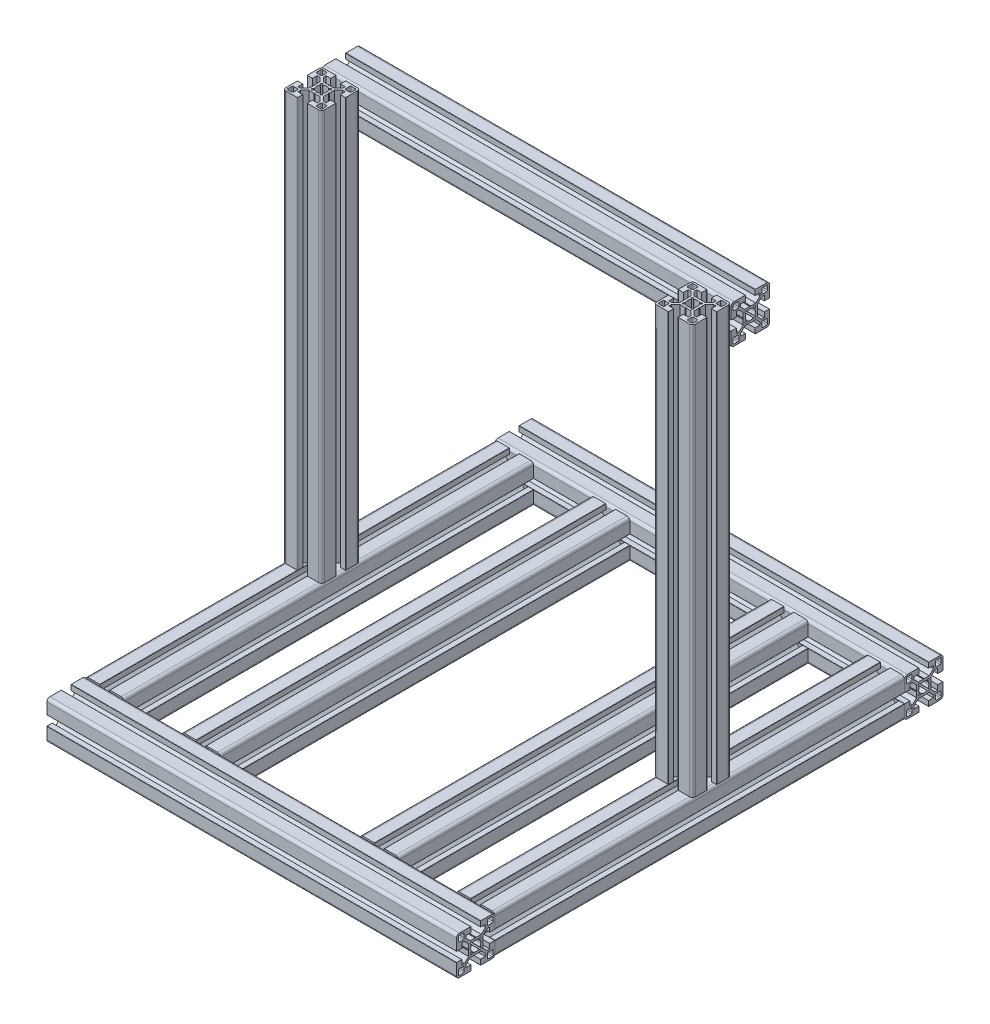
SolidWorks part; units mm, degrees
note: The reader was unsure of these and kept them because the rebuilt part matched: shared geometry of "Sketch3<2>", "Sketch5<2>".
ref_plane "Front Plane" through (0, 0, 0) normal (0, 0, 1) x (1, 0, 0)
ref_plane "Top Plane" through (0, 0, 0) normal (0, 1, 0) x (1, 0, 0)
ref_plane "Right Plane" through (0, 0, 0) normal (1, 0, 0) x (0, 0, -1)
sketch3d "3DSketch1"
  line L0 (-112.5, 0, -212.5) -> (-112.5, 0, 212.5)
  line L1 (-212.5, 0, -212.5) -> (212.5, 0, -212.5)
  line L2 (-212.5, 0, -212.5) -> (-212.5, 0, 212.5)
  line L3 (-212.5, 0, 212.5) -> (212.5, 0, 212.5)
  line L4 (212.5, 0, -212.5) -> (212.5, 0, 212.5)
  line L5 (-212.5, 0, -212.5) -> (212.5, 0, 212.5) construction
  line L6 (-212.5, 0, 212.5) -> (212.5, 0, -212.5) construction
  line L7 (112.5, 0, -212.5) -> (112.5, 0, 212.5)
  line L8 (212.5, 0, -12.5) -> (212.5, 425, -12.5)
  line L9 (-212.5, 0, -12.5) -> (-212.5, 425, -12.5)
  line L10 (212.5, 425, -12.5) -> (-212.5, 425, -12.5)
  line L11 (-212.5, 425, -12.5) -> (-212.5, 425, -32.5)
  line L13 (-212.5, 425, -32.5) -> (212.5, 425, -32.5)
  line L14 (212.5, 425, -12.5) -> (212.5, 425, -32.5)
  point P0 (0, 0, 0)
  dimension "D1" = 425
  dimension "D2" = 425
  dimension "D3" = 100
  dimension "D4" = 100
  dimension "D5" = 425
  dimension "D6" = 425
  dimension "D7" = 200
  dimension "D8" = 200
  dimension "D9" = 425
  dimension "D10" = 20
other "Lengths 1" corner treatment butt2
ref_plane "Plane2" through (-242.5, -70, -212.5) normal (0, 0, 1) x (1, 0, 0)
sketch "Profile" plane through (-242.5, -70, -212.5) normal (0, 0, 1) x (1, 0, 0)
  line L11 (37, 68) -> (33, 68)
  line L12 (69.7, 55) -> (64.5, 55)
  line L13 (64.5, 60) -> (64.5, 55)
  line L14 (70, 67) -> (70, 55.3)
  line L15 (68, 67) -> (68, 63)
  line L16 (64.5, 40) -> (64.5, 45)
  line L17 (69.7, 45) -> (64.5, 45)
  line L18 (70, 33) -> (70, 44.7)
  line L19 (68, 33) -> (68, 37)
  line L20 (33, 70) -> (44.7, 70)
  line L21 (60, 64.5) -> (60, 61.7678)
  line L22 (60, 64.5) -> (55, 64.5)
  line L23 (60, 61.7678) -> (55.7322, 57.5)
  line L24 (61.7678, 60) -> (57.5, 55.7322)
  line L25 (40, 64.5) -> (40, 61.7678)
  line L26 (40, 64.5) -> (45, 64.5)
  line L27 (40, 61.7678) -> (44.2678, 57.5)
  line L28 (35.5, 60) -> (38.2322, 60)
  line L29 (30.3, 55) -> (35.5, 55)
  line L30 (38.2322, 60) -> (42.5, 55.7322)
  line L31 (35.5, 55) -> (35.5, 60)
  line L32 (30, 67) -> (30, 55.3)
  line L33 (32, 67) -> (32, 63)
  line L34 (38, 67) -> (38, 63)
  line L35 (45, 69.7) -> (45, 64.5)
  line L36 (55, 69.7) -> (55, 64.5)
  line L37 (62, 67) -> (62, 63)
  line L38 (61.7678, 40) -> (57.5, 44.2678)
  line L39 (60, 35.5) -> (60, 38.2322)
  line L40 (60, 38.2322) -> (55.7322, 42.5)
  line L41 (55, 30.3) -> (55, 35.5)
  line L42 (62, 33) -> (62, 37)
  line L43 (38.2322, 40) -> (42.5, 44.2678)
  line L44 (40, 35.5) -> (40, 38.2322)
  line L45 (40, 35.5) -> (45, 35.5)
  line L46 (44.2678, 42.5) -> (49.4804, 42.5)
  line L47 (40, 38.2322) -> (44.2678, 42.5)
  line L48 (35.5, 45) -> (35.5, 40)
  line L49 (30.3, 45) -> (35.5, 45)
  line L50 (33, 38) -> (37, 38)
  line L51 (35.5, 40) -> (38.2322, 40)
  line L52 (33, 32) -> (37, 32)
  line L53 (33, 30) -> (44.7, 30)
  line L54 (30, 33) -> (30, 44.7)
  line L55 (32, 33) -> (32, 37)
  line L56 (38, 33) -> (38, 37)
  line L57 (45, 30.3) -> (45, 35.5)
  line L58 (50, 75) -> (50, 25) construction
  line L59 (57.5, 55.7322) -> (57.5, 50.5196)
  line L60 (67, 38) -> (63, 38)
  line L61 (25, 50) -> (75, 50) construction
  line L62 (64.5, 40) -> (61.7678, 40)
  line L63 (67, 62) -> (63, 62)
  line L64 (64.5, 60) -> (61.7678, 60)
  line L65 (42.5, 44.2678) -> (42.5, 49.4804)
  line L66 (37, 62) -> (33, 62)
  line L67 (44.2678, 57.5) -> (49.4804, 57.5)
  line L68 (57.5, 49.4804) -> (57.5, 44.2678)
  line L69 (42.5, 50.5196) -> (42.5, 55.7322)
  line L70 (50.5196, 57.5) -> (55.7322, 57.5)
  line L71 (55.3, 70) -> (67, 70)
  line L72 (63, 68) -> (67, 68)
  line L73 (55.3, 30) -> (67, 30)
  line L74 (63, 32) -> (67, 32)
  line L75 (55, 35.5) -> (60, 35.5)
  line L76 (50.5196, 42.5) -> (55.7322, 42.5)
  line L77 (57.2, 50) -> (57.5, 50.5196)
  line L78 (57.2, 50) -> (57.5, 49.4804)
  line L79 (42.8, 50) -> (42.5, 50.5196)
  line L80 (42.8, 50) -> (42.5, 49.4804)
  line L81 (50, 57.2) -> (49.4804, 57.5)
  line L82 (50, 57.2) -> (50.5196, 57.5)
  line L83 (50, 42.8) -> (49.4804, 42.5)
  line L84 (50, 42.8) -> (50.5196, 42.5)
  arc A0 (69.7, 55) -> (70, 55.3) centre (69.7, 55.3) ccw
  arc A1 (68, 67) -> (67, 68) centre (67, 67) ccw
  arc A2 (70, 44.7) -> (69.7, 45) centre (69.7, 44.7) ccw
  arc A3 (68, 37) -> (67, 38) centre (67, 37) ccw
  arc A4 (62, 63) -> (63, 62) centre (63, 63) ccw
  arc A5 (30, 55.3) -> (30.3, 55) centre (30.3, 55.3) ccw
  arc A6 (37, 62) -> (38, 63) centre (37, 63) ccw
  arc A7 (38, 67) -> (37, 68) centre (37, 67) ccw
  arc A8 (62, 33) -> (63, 32) centre (63, 33) ccw
  arc A9 (30.3, 45) -> (30, 44.7) centre (30.3, 44.7) ccw
  arc A10 (38, 37) -> (37, 38) centre (37, 37) ccw
  arc A11 (32, 33) -> (33, 32) centre (33, 33) ccw
  arc A12 (37, 32) -> (38, 33) centre (37, 33) ccw
  arc A13 (33, 38) -> (32, 37) centre (33, 37) ccw
  arc A14 (63, 38) -> (62, 37) centre (63, 37) ccw
  arc A15 (67, 62) -> (68, 63) centre (67, 63) ccw
  arc A16 (30, 33) -> (33, 30) centre (33, 33) ccw
  arc A17 (44.7, 30) -> (45, 30.3) centre (44.7, 30.3) ccw
  arc A18 (32, 63) -> (33, 62) centre (33, 63) ccw
  arc A19 (33, 68) -> (32, 67) centre (33, 67) ccw
  arc A20 (45, 69.7) -> (44.7, 70) centre (44.7, 69.7) ccw
  arc A21 (33, 70) -> (30, 67) centre (33, 67) ccw
  arc A22 (63, 68) -> (62, 67) centre (63, 67) ccw
  arc A23 (67, 32) -> (68, 33) centre (67, 33) ccw
  arc A24 (55, 30.3) -> (55.3, 30) centre (55.3, 30.3) ccw
  arc A25 (55.3, 70) -> (55, 69.7) centre (55.3, 69.7) ccw
  arc A26 (67, 30) -> (70, 33) centre (67, 33) ccw
  arc A27 (70, 67) -> (67, 70) centre (67, 67) ccw
  arc A28 (45.694, 53.0035) -> (45.694, 46.9966) centre (50, 50) ccw
  arc A29 (46.9981, 45.6929) -> (53.0039, 45.6943) centre (50, 50) ccw
  arc A30 (54.3061, 46.9967) -> (54.3061, 53.0034) centre (50, 50) ccw
  arc A31 (53.0033, 54.3061) -> (46.9968, 54.3062) centre (50, 50) ccw
  arc A32 (46.4038, 54.6058) -> (45.3944, 53.5962) centre (45.4038, 54.5962) ccw
  arc A33 (54.608, 53.5963) -> (53.5962, 54.6065) centre (54.5962, 54.5962) ccw
  arc A34 (53.5962, 45.3942) -> (54.6061, 46.4038) centre (54.5962, 45.4038) ccw
  arc A35 (45.3939, 46.4038) -> (46.4038, 45.3942) centre (45.4038, 45.4038) ccw
  arc A36 (45.694, 53.0035) -> (45.3944, 53.5962) centre (45.3778, 53.2158) ccw
  arc A37 (46.4038, 54.6058) -> (46.9968, 54.3062) centre (46.7842, 54.6222) ccw
  arc A38 (54.608, 53.5963) -> (54.3061, 53.0034) centre (54.6221, 53.2158) ccw
  arc A39 (53.0033, 54.3061) -> (53.5962, 54.6065) centre (53.2158, 54.6221) ccw
  arc A40 (45.3939, 46.4038) -> (45.694, 46.9966) centre (45.3778, 46.7842) ccw
  arc A41 (46.9981, 45.6929) -> (46.4038, 45.3942) centre (46.7842, 45.3779) ccw
  arc A42 (54.3061, 46.9967) -> (54.6061, 46.4038) centre (54.6222, 46.7842) ccw
  arc A43 (53.5962, 45.3942) -> (53.0039, 45.6943) centre (53.2158, 45.3778) ccw
  point P109 (30, 70)
  point P110 (30, 30)
  point P111 (70, 30)
  point P112 (70, 70)
  point P113 (0, 0)
other "Lengths 2" corner treatment butt2
ref_plane "Plane3" through (42.5, -70, -212.5) normal (0, 0, 1) x (1, 0, 0)
sketch "Profile1" plane through (42.5, -70, -212.5) normal (0, 0, 1) x (1, 0, 0)
  line L11 (37, 68) -> (33, 68)
  line L12 (69.7, 55) -> (64.5, 55)
  line L13 (64.5, 60) -> (64.5, 55)
  line L14 (70, 67) -> (70, 55.3)
  line L15 (68, 67) -> (68, 63)
  line L16 (64.5, 40) -> (64.5, 45)
  line L17 (69.7, 45) -> (64.5, 45)
  line L18 (70, 33) -> (70, 44.7)
  line L19 (68, 33) -> (68, 37)
  line L20 (33, 70) -> (44.7, 70)
  line L21 (60, 64.5) -> (60, 61.7678)
  line L22 (60, 64.5) -> (55, 64.5)
  line L23 (60, 61.7678) -> (55.7322, 57.5)
  line L24 (61.7678, 60) -> (57.5, 55.7322)
  line L25 (40, 64.5) -> (40, 61.7678)
  line L26 (40, 64.5) -> (45, 64.5)
  line L27 (40, 61.7678) -> (44.2678, 57.5)
  line L28 (35.5, 60) -> (38.2322, 60)
  line L29 (30.3, 55) -> (35.5, 55)
  line L30 (38.2322, 60) -> (42.5, 55.7322)
  line L31 (35.5, 55) -> (35.5, 60)
  line L32 (30, 67) -> (30, 55.3)
  line L33 (32, 67) -> (32, 63)
  line L34 (38, 67) -> (38, 63)
  line L35 (45, 69.7) -> (45, 64.5)
  line L36 (55, 69.7) -> (55, 64.5)
  line L37 (62, 67) -> (62, 63)
  line L38 (61.7678, 40) -> (57.5, 44.2678)
  line L39 (60, 35.5) -> (60, 38.2322)
  line L40 (60, 38.2322) -> (55.7322, 42.5)
  line L41 (55, 30.3) -> (55, 35.5)
  line L42 (62, 33) -> (62, 37)
  line L43 (38.2322, 40) -> (42.5, 44.2678)
  line L44 (40, 35.5) -> (40, 38.2322)
  line L45 (40, 35.5) -> (45, 35.5)
  line L46 (44.2678, 42.5) -> (49.4804, 42.5)
  line L47 (40, 38.2322) -> (44.2678, 42.5)
  line L48 (35.5, 45) -> (35.5, 40)
  line L49 (30.3, 45) -> (35.5, 45)
  line L50 (33, 38) -> (37, 38)
  line L51 (35.5, 40) -> (38.2322, 40)
  line L52 (33, 32) -> (37, 32)
  line L53 (33, 30) -> (44.7, 30)
  line L54 (30, 33) -> (30, 44.7)
  line L55 (32, 33) -> (32, 37)
  line L56 (38, 33) -> (38, 37)
  line L57 (45, 30.3) -> (45, 35.5)
  line L58 (50, 75) -> (50, 25) construction
  line L59 (57.5, 55.7322) -> (57.5, 50.5196)
  line L60 (67, 38) -> (63, 38)
  line L61 (25, 50) -> (75, 50) construction
  line L62 (64.5, 40) -> (61.7678, 40)
  line L63 (67, 62) -> (63, 62)
  line L64 (64.5, 60) -> (61.7678, 60)
  line L65 (42.5, 44.2678) -> (42.5, 49.4804)
  line L66 (37, 62) -> (33, 62)
  line L67 (44.2678, 57.5) -> (49.4804, 57.5)
  line L68 (57.5, 49.4804) -> (57.5, 44.2678)
  line L69 (42.5, 50.5196) -> (42.5, 55.7322)
  line L70 (50.5196, 57.5) -> (55.7322, 57.5)
  line L71 (55.3, 70) -> (67, 70)
  line L72 (63, 68) -> (67, 68)
  line L73 (55.3, 30) -> (67, 30)
  line L74 (63, 32) -> (67, 32)
  line L75 (55, 35.5) -> (60, 35.5)
  line L76 (50.5196, 42.5) -> (55.7322, 42.5)
  line L77 (57.2, 50) -> (57.5, 50.5196)
  line L78 (57.2, 50) -> (57.5, 49.4804)
  line L79 (42.8, 50) -> (42.5, 50.5196)
  line L80 (42.8, 50) -> (42.5, 49.4804)
  line L81 (50, 57.2) -> (49.4804, 57.5)
  line L82 (50, 57.2) -> (50.5196, 57.5)
  line L83 (50, 42.8) -> (49.4804, 42.5)
  line L84 (50, 42.8) -> (50.5196, 42.5)
  arc A0 (69.7, 55) -> (70, 55.3) centre (69.7, 55.3) ccw
  arc A1 (68, 67) -> (67, 68) centre (67, 67) ccw
  arc A2 (70, 44.7) -> (69.7, 45) centre (69.7, 44.7) ccw
  arc A3 (68, 37) -> (67, 38) centre (67, 37) ccw
  arc A4 (62, 63) -> (63, 62) centre (63, 63) ccw
  arc A5 (30, 55.3) -> (30.3, 55) centre (30.3, 55.3) ccw
  arc A6 (37, 62) -> (38, 63) centre (37, 63) ccw
  arc A7 (38, 67) -> (37, 68) centre (37, 67) ccw
  arc A8 (62, 33) -> (63, 32) centre (63, 33) ccw
  arc A9 (30.3, 45) -> (30, 44.7) centre (30.3, 44.7) ccw
  arc A10 (38, 37) -> (37, 38) centre (37, 37) ccw
  arc A11 (32, 33) -> (33, 32) centre (33, 33) ccw
  arc A12 (37, 32) -> (38, 33) centre (37, 33) ccw
  arc A13 (33, 38) -> (32, 37) centre (33, 37) ccw
  arc A14 (63, 38) -> (62, 37) centre (63, 37) ccw
  arc A15 (67, 62) -> (68, 63) centre (67, 63) ccw
  arc A16 (30, 33) -> (33, 30) centre (33, 33) ccw
  arc A17 (44.7, 30) -> (45, 30.3) centre (44.7, 30.3) ccw
  arc A18 (32, 63) -> (33, 62) centre (33, 63) ccw
  arc A19 (33, 68) -> (32, 67) centre (33, 67) ccw
  arc A20 (45, 69.7) -> (44.7, 70) centre (44.7, 69.7) ccw
  arc A21 (33, 70) -> (30, 67) centre (33, 67) ccw
  arc A22 (63, 68) -> (62, 67) centre (63, 67) ccw
  arc A23 (67, 32) -> (68, 33) centre (67, 33) ccw
  arc A24 (55, 30.3) -> (55.3, 30) centre (55.3, 30.3) ccw
  arc A25 (55.3, 70) -> (55, 69.7) centre (55.3, 69.7) ccw
  arc A26 (67, 30) -> (70, 33) centre (67, 33) ccw
  arc A27 (70, 67) -> (67, 70) centre (67, 67) ccw
  arc A28 (45.694, 53.0035) -> (45.694, 46.9966) centre (50, 50) ccw
  arc A29 (46.9981, 45.6929) -> (53.0039, 45.6943) centre (50, 50) ccw
  arc A30 (54.3061, 46.9967) -> (54.3061, 53.0034) centre (50, 50) ccw
  arc A31 (53.0033, 54.3061) -> (46.9968, 54.3062) centre (50, 50) ccw
  arc A32 (46.4038, 54.6058) -> (45.3944, 53.5962) centre (45.4038, 54.5962) ccw
  arc A33 (54.608, 53.5963) -> (53.5962, 54.6065) centre (54.5962, 54.5962) ccw
  arc A34 (53.5962, 45.3942) -> (54.6061, 46.4038) centre (54.5962, 45.4038) ccw
  arc A35 (45.3939, 46.4038) -> (46.4038, 45.3942) centre (45.4038, 45.4038) ccw
  arc A36 (45.694, 53.0035) -> (45.3944, 53.5962) centre (45.3778, 53.2158) ccw
  arc A37 (46.4038, 54.6058) -> (46.9968, 54.3062) centre (46.7842, 54.6222) ccw
  arc A38 (54.608, 53.5963) -> (54.3061, 53.0034) centre (54.6221, 53.2158) ccw
  arc A39 (53.0033, 54.3061) -> (53.5962, 54.6065) centre (53.2158, 54.6221) ccw
  arc A40 (45.3939, 46.4038) -> (45.694, 46.9966) centre (45.3778, 46.7842) ccw
  arc A41 (46.9981, 45.6929) -> (46.4038, 45.3942) centre (46.7842, 45.3779) ccw
  arc A42 (54.3061, 46.9967) -> (54.6061, 46.4038) centre (54.6222, 46.7842) ccw
  arc A43 (53.5962, 45.3942) -> (53.0039, 45.6943) centre (53.2158, 45.3778) ccw
  point P109 (30, 70)
  point P110 (30, 30)
  point P111 (70, 30)
  point P112 (70, 70)
  point P113 (0, 0)
other "Back" corner treatment butt2
ref_plane "Plane4" through (-212.5, -70, -182.5) normal (1, 0, 0) x (0, 0, -1)
sketch "Profile2" plane through (-212.5, -70, -182.5) normal (1, 0, 0) x (0, 0, -1)
  line L11 (37, 68) -> (33, 68)
  line L12 (69.7, 55) -> (64.5, 55)
  line L13 (64.5, 60) -> (64.5, 55)
  line L14 (70, 67) -> (70, 55.3)
  line L15 (68, 67) -> (68, 63)
  line L16 (64.5, 40) -> (64.5, 45)
  line L17 (69.7, 45) -> (64.5, 45)
  line L18 (70, 33) -> (70, 44.7)
  line L19 (68, 33) -> (68, 37)
  line L20 (33, 70) -> (44.7, 70)
  line L21 (60, 64.5) -> (60, 61.7678)
  line L22 (60, 64.5) -> (55, 64.5)
  line L23 (60, 61.7678) -> (55.7322, 57.5)
  line L24 (61.7678, 60) -> (57.5, 55.7322)
  line L25 (40, 64.5) -> (40, 61.7678)
  line L26 (40, 64.5) -> (45, 64.5)
  line L27 (40, 61.7678) -> (44.2678, 57.5)
  line L28 (35.5, 60) -> (38.2322, 60)
  line L29 (30.3, 55) -> (35.5, 55)
  line L30 (38.2322, 60) -> (42.5, 55.7322)
  line L31 (35.5, 55) -> (35.5, 60)
  line L32 (30, 67) -> (30, 55.3)
  line L33 (32, 67) -> (32, 63)
  line L34 (38, 67) -> (38, 63)
  line L35 (45, 69.7) -> (45, 64.5)
  line L36 (55, 69.7) -> (55, 64.5)
  line L37 (62, 67) -> (62, 63)
  line L38 (61.7678, 40) -> (57.5, 44.2678)
  line L39 (60, 35.5) -> (60, 38.2322)
  line L40 (60, 38.2322) -> (55.7322, 42.5)
  line L41 (55, 30.3) -> (55, 35.5)
  line L42 (62, 33) -> (62, 37)
  line L43 (38.2322, 40) -> (42.5, 44.2678)
  line L44 (40, 35.5) -> (40, 38.2322)
  line L45 (40, 35.5) -> (45, 35.5)
  line L46 (44.2678, 42.5) -> (49.4804, 42.5)
  line L47 (40, 38.2322) -> (44.2678, 42.5)
  line L48 (35.5, 45) -> (35.5, 40)
  line L49 (30.3, 45) -> (35.5, 45)
  line L50 (33, 38) -> (37, 38)
  line L51 (35.5, 40) -> (38.2322, 40)
  line L52 (33, 32) -> (37, 32)
  line L53 (33, 30) -> (44.7, 30)
  line L54 (30, 33) -> (30, 44.7)
  line L55 (32, 33) -> (32, 37)
  line L56 (38, 33) -> (38, 37)
  line L57 (45, 30.3) -> (45, 35.5)
  line L58 (50, 75) -> (50, 25) construction
  line L59 (57.5, 55.7322) -> (57.5, 50.5196)
  line L60 (67, 38) -> (63, 38)
  line L61 (25, 50) -> (75, 50) construction
  line L62 (64.5, 40) -> (61.7678, 40)
  line L63 (67, 62) -> (63, 62)
  line L64 (64.5, 60) -> (61.7678, 60)
  line L65 (42.5, 44.2678) -> (42.5, 49.4804)
  line L66 (37, 62) -> (33, 62)
  line L67 (44.2678, 57.5) -> (49.4804, 57.5)
  line L68 (57.5, 49.4804) -> (57.5, 44.2678)
  line L69 (42.5, 50.5196) -> (42.5, 55.7322)
  line L70 (50.5196, 57.5) -> (55.7322, 57.5)
  line L71 (55.3, 70) -> (67, 70)
  line L72 (63, 68) -> (67, 68)
  line L73 (55.3, 30) -> (67, 30)
  line L74 (63, 32) -> (67, 32)
  line L75 (55, 35.5) -> (60, 35.5)
  line L76 (50.5196, 42.5) -> (55.7322, 42.5)
  line L77 (57.2, 50) -> (57.5, 50.5196)
  line L78 (57.2, 50) -> (57.5, 49.4804)
  line L79 (42.8, 50) -> (42.5, 50.5196)
  line L80 (42.8, 50) -> (42.5, 49.4804)
  line L81 (50, 57.2) -> (49.4804, 57.5)
  line L82 (50, 57.2) -> (50.5196, 57.5)
  line L83 (50, 42.8) -> (49.4804, 42.5)
  line L84 (50, 42.8) -> (50.5196, 42.5)
  arc A0 (69.7, 55) -> (70, 55.3) centre (69.7, 55.3) ccw
  arc A1 (68, 67) -> (67, 68) centre (67, 67) ccw
  arc A2 (70, 44.7) -> (69.7, 45) centre (69.7, 44.7) ccw
  arc A3 (68, 37) -> (67, 38) centre (67, 37) ccw
  arc A4 (62, 63) -> (63, 62) centre (63, 63) ccw
  arc A5 (30, 55.3) -> (30.3, 55) centre (30.3, 55.3) ccw
  arc A6 (37, 62) -> (38, 63) centre (37, 63) ccw
  arc A7 (38, 67) -> (37, 68) centre (37, 67) ccw
  arc A8 (62, 33) -> (63, 32) centre (63, 33) ccw
  arc A9 (30.3, 45) -> (30, 44.7) centre (30.3, 44.7) ccw
  arc A10 (38, 37) -> (37, 38) centre (37, 37) ccw
  arc A11 (32, 33) -> (33, 32) centre (33, 33) ccw
  arc A12 (37, 32) -> (38, 33) centre (37, 33) ccw
  arc A13 (33, 38) -> (32, 37) centre (33, 37) ccw
  arc A14 (63, 38) -> (62, 37) centre (63, 37) ccw
  arc A15 (67, 62) -> (68, 63) centre (67, 63) ccw
  arc A16 (30, 33) -> (33, 30) centre (33, 33) ccw
  arc A17 (44.7, 30) -> (45, 30.3) centre (44.7, 30.3) ccw
  arc A18 (32, 63) -> (33, 62) centre (33, 63) ccw
  arc A19 (33, 68) -> (32, 67) centre (33, 67) ccw
  arc A20 (45, 69.7) -> (44.7, 70) centre (44.7, 69.7) ccw
  arc A21 (33, 70) -> (30, 67) centre (33, 67) ccw
  arc A22 (63, 68) -> (62, 67) centre (63, 67) ccw
  arc A23 (67, 32) -> (68, 33) centre (67, 33) ccw
  arc A24 (55, 30.3) -> (55.3, 30) centre (55.3, 30.3) ccw
  arc A25 (55.3, 70) -> (55, 69.7) centre (55.3, 69.7) ccw
  arc A26 (67, 30) -> (70, 33) centre (67, 33) ccw
  arc A27 (70, 67) -> (67, 70) centre (67, 67) ccw
  arc A28 (45.694, 53.0035) -> (45.694, 46.9966) centre (50, 50) ccw
  arc A29 (46.9981, 45.6929) -> (53.0039, 45.6943) centre (50, 50) ccw
  arc A30 (54.3061, 46.9967) -> (54.3061, 53.0034) centre (50, 50) ccw
  arc A31 (53.0033, 54.3061) -> (46.9968, 54.3062) centre (50, 50) ccw
  arc A32 (46.4038, 54.6058) -> (45.3944, 53.5962) centre (45.4038, 54.5962) ccw
  arc A33 (54.608, 53.5963) -> (53.5962, 54.6065) centre (54.5962, 54.5962) ccw
  arc A34 (53.5962, 45.3942) -> (54.6061, 46.4038) centre (54.5962, 45.4038) ccw
  arc A35 (45.3939, 46.4038) -> (46.4038, 45.3942) centre (45.4038, 45.4038) ccw
  arc A36 (45.694, 53.0035) -> (45.3944, 53.5962) centre (45.3778, 53.2158) ccw
  arc A37 (46.4038, 54.6058) -> (46.9968, 54.3062) centre (46.7842, 54.6222) ccw
  arc A38 (54.608, 53.5963) -> (54.3061, 53.0034) centre (54.6221, 53.2158) ccw
  arc A39 (53.0033, 54.3061) -> (53.5962, 54.6065) centre (53.2158, 54.6221) ccw
  arc A40 (45.3939, 46.4038) -> (45.694, 46.9966) centre (45.3778, 46.7842) ccw
  arc A41 (46.9981, 45.6929) -> (46.4038, 45.3942) centre (46.7842, 45.3779) ccw
  arc A42 (54.3061, 46.9967) -> (54.6061, 46.4038) centre (54.6222, 46.7842) ccw
  arc A43 (53.5962, 45.3942) -> (53.0039, 45.6943) centre (53.2158, 45.3778) ccw
  point P109 (30, 70)
  point P110 (30, 30)
  point P111 (70, 30)
  point P112 (70, 70)
  point P113 (0, 0)
other "Front" corner treatment butt2
ref_plane "Plane5" through (-212.5, -70, 282.5) normal (1, 0, 0) x (0, 0, -1)
sketch "Profile7" plane through (-212.5, -70, 282.5) normal (1, 0, 0) x (0, 0, -1)
  line L11 (37, 68) -> (33, 68)
  line L12 (69.7, 55) -> (64.5, 55)
  line L13 (64.5, 60) -> (64.5, 55)
  line L14 (70, 67) -> (70, 55.3)
  line L15 (68, 67) -> (68, 63)
  line L16 (64.5, 40) -> (64.5, 45)
  line L17 (69.7, 45) -> (64.5, 45)
  line L18 (70, 33) -> (70, 44.7)
  line L19 (68, 33) -> (68, 37)
  line L20 (33, 70) -> (44.7, 70)
  line L21 (60, 64.5) -> (60, 61.7678)
  line L22 (60, 64.5) -> (55, 64.5)
  line L23 (60, 61.7678) -> (55.7322, 57.5)
  line L24 (61.7678, 60) -> (57.5, 55.7322)
  line L25 (40, 64.5) -> (40, 61.7678)
  line L26 (40, 64.5) -> (45, 64.5)
  line L27 (40, 61.7678) -> (44.2678, 57.5)
  line L28 (35.5, 60) -> (38.2322, 60)
  line L29 (30.3, 55) -> (35.5, 55)
  line L30 (38.2322, 60) -> (42.5, 55.7322)
  line L31 (35.5, 55) -> (35.5, 60)
  line L32 (30, 67) -> (30, 55.3)
  line L33 (32, 67) -> (32, 63)
  line L34 (38, 67) -> (38, 63)
  line L35 (45, 69.7) -> (45, 64.5)
  line L36 (55, 69.7) -> (55, 64.5)
  line L37 (62, 67) -> (62, 63)
  line L38 (61.7678, 40) -> (57.5, 44.2678)
  line L39 (60, 35.5) -> (60, 38.2322)
  line L40 (60, 38.2322) -> (55.7322, 42.5)
  line L41 (55, 30.3) -> (55, 35.5)
  line L42 (62, 33) -> (62, 37)
  line L43 (38.2322, 40) -> (42.5, 44.2678)
  line L44 (40, 35.5) -> (40, 38.2322)
  line L45 (40, 35.5) -> (45, 35.5)
  line L46 (44.2678, 42.5) -> (49.4804, 42.5)
  line L47 (40, 38.2322) -> (44.2678, 42.5)
  line L48 (35.5, 45) -> (35.5, 40)
  line L49 (30.3, 45) -> (35.5, 45)
  line L50 (33, 38) -> (37, 38)
  line L51 (35.5, 40) -> (38.2322, 40)
  line L52 (33, 32) -> (37, 32)
  line L53 (33, 30) -> (44.7, 30)
  line L54 (30, 33) -> (30, 44.7)
  line L55 (32, 33) -> (32, 37)
  line L56 (38, 33) -> (38, 37)
  line L57 (45, 30.3) -> (45, 35.5)
  line L58 (50, 70) -> (50, 30) construction
  line L59 (57.5, 55.7322) -> (57.5, 50.5196)
  line L60 (67, 38) -> (63, 38)
  line L61 (30, 50) -> (70, 50) construction
  line L62 (64.5, 40) -> (61.7678, 40)
  line L63 (67, 62) -> (63, 62)
  line L64 (64.5, 60) -> (61.7678, 60)
  line L65 (42.5, 44.2678) -> (42.5, 49.4804)
  line L66 (37, 62) -> (33, 62)
  line L67 (44.2678, 57.5) -> (49.4804, 57.5)
  line L68 (57.5, 49.4804) -> (57.5, 44.2678)
  line L69 (42.5, 50.5196) -> (42.5, 55.7322)
  line L70 (50.5196, 57.5) -> (55.7322, 57.5)
  line L71 (55.3, 70) -> (67, 70)
  line L72 (63, 68) -> (67, 68)
  line L73 (55.3, 30) -> (67, 30)
  line L74 (63, 32) -> (67, 32)
  line L75 (55, 35.5) -> (60, 35.5)
  line L76 (50.5196, 42.5) -> (55.7322, 42.5)
  line L77 (57.2, 50) -> (57.5, 50.5196)
  line L78 (57.2, 50) -> (57.5, 49.4804)
  line L79 (42.8, 50) -> (42.5, 50.5196)
  line L80 (42.8, 50) -> (42.5, 49.4804)
  line L81 (50, 57.2) -> (49.4804, 57.5)
  line L82 (50, 57.2) -> (50.5196, 57.5)
  line L83 (50, 42.8) -> (49.4804, 42.5)
  line L84 (50, 42.8) -> (50.5196, 42.5)
  arc A0 (69.7, 55) -> (70, 55.3) centre (69.7, 55.3) ccw
  arc A1 (68, 67) -> (67, 68) centre (67, 67) ccw
  arc A2 (70, 44.7) -> (69.7, 45) centre (69.7, 44.7) ccw
  arc A3 (68, 37) -> (67, 38) centre (67, 37) ccw
  arc A4 (62, 63) -> (63, 62) centre (63, 63) ccw
  arc A5 (30, 55.3) -> (30.3, 55) centre (30.3, 55.3) ccw
  arc A6 (37, 62) -> (38, 63) centre (37, 63) ccw
  arc A7 (38, 67) -> (37, 68) centre (37, 67) ccw
  arc A8 (62, 33) -> (63, 32) centre (63, 33) ccw
  arc A9 (30.3, 45) -> (30, 44.7) centre (30.3, 44.7) ccw
  arc A10 (38, 37) -> (37, 38) centre (37, 37) ccw
  arc A11 (32, 33) -> (33, 32) centre (33, 33) ccw
  arc A12 (37, 32) -> (38, 33) centre (37, 33) ccw
  arc A13 (33, 38) -> (32, 37) centre (33, 37) ccw
  arc A14 (63, 38) -> (62, 37) centre (63, 37) ccw
  arc A15 (67, 62) -> (68, 63) centre (67, 63) ccw
  arc A16 (30, 33) -> (33, 30) centre (33, 33) ccw
  arc A17 (44.7, 30) -> (45, 30.3) centre (44.7, 30.3) ccw
  arc A18 (32, 63) -> (33, 62) centre (33, 63) ccw
  arc A19 (33, 68) -> (32, 67) centre (33, 67) ccw
  arc A20 (45, 69.7) -> (44.7, 70) centre (44.7, 69.7) ccw
  arc A21 (33, 70) -> (30, 67) centre (33, 67) ccw
  arc A22 (63, 68) -> (62, 67) centre (63, 67) ccw
  arc A23 (67, 32) -> (68, 33) centre (67, 33) ccw
  arc A24 (55, 30.3) -> (55.3, 30) centre (55.3, 30.3) ccw
  arc A25 (55.3, 70) -> (55, 69.7) centre (55.3, 69.7) ccw
  arc A26 (67, 30) -> (70, 33) centre (67, 33) ccw
  arc A27 (70, 67) -> (67, 70) centre (67, 67) ccw
  arc A28 (45.694, 53.0035) -> (45.694, 46.9966) centre (50, 50) ccw
  arc A29 (46.9981, 45.6929) -> (53.0039, 45.6943) centre (50, 50) ccw
  arc A30 (54.3061, 46.9967) -> (54.3061, 53.0034) centre (50, 50) ccw
  arc A31 (53.0033, 54.3061) -> (46.9968, 54.3062) centre (50, 50) ccw
  arc A32 (46.4038, 54.6058) -> (45.3944, 53.5962) centre (45.4038, 54.5962) ccw
  arc A33 (54.608, 53.5963) -> (53.5962, 54.6065) centre (54.5962, 54.5962) ccw
  arc A34 (53.5962, 45.3942) -> (54.6061, 46.4038) centre (54.5962, 45.4038) ccw
  arc A35 (45.3939, 46.4038) -> (46.4038, 45.3942) centre (45.4038, 45.4038) ccw
  arc A36 (45.694, 53.0035) -> (45.3944, 53.5962) centre (45.3778, 53.2158) ccw
  arc A37 (46.4038, 54.6058) -> (46.9968, 54.3062) centre (46.7842, 54.6222) ccw
  arc A38 (54.608, 53.5963) -> (54.3061, 53.0034) centre (54.6221, 53.2158) ccw
  arc A39 (53.0033, 54.3061) -> (53.5962, 54.6065) centre (53.2158, 54.6221) ccw
  arc A40 (45.3939, 46.4038) -> (45.694, 46.9966) centre (45.3778, 46.7842) ccw
  arc A41 (46.9981, 45.6929) -> (46.4038, 45.3942) centre (46.7842, 45.3779) ccw
  arc A42 (54.3061, 46.9967) -> (54.6061, 46.4038) centre (54.6222, 46.7842) ccw
  arc A43 (53.5962, 45.3942) -> (53.0039, 45.6943) centre (53.2158, 45.3778) ccw
  point P109 (30, 70)
  point P110 (30, 30)
  point P111 (70, 30)
  point P112 (70, 70)
  point P113 (0, 0)
other "Upright 1" corner treatment butt2
ref_plane "Plane6" through (-242.5, 0, 37.5) normal (0, 1, 0) x (1, 0, 0)
sketch "Profile5" plane through (-242.5, 0, 37.5) normal (0, 1, 0) x (1, 0, 0)
  line L11 (37, 68) -> (33, 68)
  line L12 (69.7, 55) -> (64.5, 55)
  line L13 (64.5, 60) -> (64.5, 55)
  line L14 (70, 67) -> (70, 55.3)
  line L15 (68, 67) -> (68, 63)
  line L16 (64.5, 40) -> (64.5, 45)
  line L17 (69.7, 45) -> (64.5, 45)
  line L18 (70, 33) -> (70, 44.7)
  line L19 (68, 33) -> (68, 37)
  line L20 (33, 70) -> (44.7, 70)
  line L21 (60, 64.5) -> (60, 61.7678)
  line L22 (60, 64.5) -> (55, 64.5)
  line L23 (60, 61.7678) -> (55.7322, 57.5)
  line L24 (61.7678, 60) -> (57.5, 55.7322)
  line L25 (40, 64.5) -> (40, 61.7678)
  line L26 (40, 64.5) -> (45, 64.5)
  line L27 (40, 61.7678) -> (44.2678, 57.5)
  line L28 (35.5, 60) -> (38.2322, 60)
  line L29 (30.3, 55) -> (35.5, 55)
  line L30 (38.2322, 60) -> (42.5, 55.7322)
  line L31 (35.5, 55) -> (35.5, 60)
  line L32 (30, 67) -> (30, 55.3)
  line L33 (32, 67) -> (32, 63)
  line L34 (38, 67) -> (38, 63)
  line L35 (45, 69.7) -> (45, 64.5)
  line L36 (55, 69.7) -> (55, 64.5)
  line L37 (62, 67) -> (62, 63)
  line L38 (61.7678, 40) -> (57.5, 44.2678)
  line L39 (60, 35.5) -> (60, 38.2322)
  line L40 (60, 38.2322) -> (55.7322, 42.5)
  line L41 (55, 30.3) -> (55, 35.5)
  line L42 (62, 33) -> (62, 37)
  line L43 (38.2322, 40) -> (42.5, 44.2678)
  line L44 (40, 35.5) -> (40, 38.2322)
  line L45 (40, 35.5) -> (45, 35.5)
  line L46 (44.2678, 42.5) -> (49.4804, 42.5)
  line L47 (40, 38.2322) -> (44.2678, 42.5)
  line L48 (35.5, 45) -> (35.5, 40)
  line L49 (30.3, 45) -> (35.5, 45)
  line L50 (33, 38) -> (37, 38)
  line L51 (35.5, 40) -> (38.2322, 40)
  line L52 (33, 32) -> (37, 32)
  line L53 (33, 30) -> (44.7, 30)
  line L54 (30, 33) -> (30, 44.7)
  line L55 (32, 33) -> (32, 37)
  line L56 (38, 33) -> (38, 37)
  line L57 (45, 30.3) -> (45, 35.5)
  line L58 (50, 70) -> (50, 30) construction
  line L59 (57.5, 55.7322) -> (57.5, 50.5196)
  line L60 (67, 38) -> (63, 38)
  line L61 (30, 50) -> (70, 50) construction
  line L62 (64.5, 40) -> (61.7678, 40)
  line L63 (67, 62) -> (63, 62)
  line L64 (64.5, 60) -> (61.7678, 60)
  line L65 (42.5, 44.2678) -> (42.5, 49.4804)
  line L66 (37, 62) -> (33, 62)
  line L67 (44.2678, 57.5) -> (49.4804, 57.5)
  line L68 (57.5, 49.4804) -> (57.5, 44.2678)
  line L69 (42.5, 50.5196) -> (42.5, 55.7322)
  line L70 (50.5196, 57.5) -> (55.7322, 57.5)
  line L71 (55.3, 70) -> (67, 70)
  line L72 (63, 68) -> (67, 68)
  line L73 (55.3, 30) -> (67, 30)
  line L74 (63, 32) -> (67, 32)
  line L75 (55, 35.5) -> (60, 35.5)
  line L76 (50.5196, 42.5) -> (55.7322, 42.5)
  line L77 (57.2, 50) -> (57.5, 50.5196)
  line L78 (57.2, 50) -> (57.5, 49.4804)
  line L79 (42.8, 50) -> (42.5, 50.5196)
  line L80 (42.8, 50) -> (42.5, 49.4804)
  line L81 (50, 57.2) -> (49.4804, 57.5)
  line L82 (50, 57.2) -> (50.5196, 57.5)
  line L83 (50, 42.8) -> (49.4804, 42.5)
  line L84 (50, 42.8) -> (50.5196, 42.5)
  arc A0 (69.7, 55) -> (70, 55.3) centre (69.7, 55.3) ccw
  arc A1 (68, 67) -> (67, 68) centre (67, 67) ccw
  arc A2 (70, 44.7) -> (69.7, 45) centre (69.7, 44.7) ccw
  arc A3 (68, 37) -> (67, 38) centre (67, 37) ccw
  arc A4 (62, 63) -> (63, 62) centre (63, 63) ccw
  arc A5 (30, 55.3) -> (30.3, 55) centre (30.3, 55.3) ccw
  arc A6 (37, 62) -> (38, 63) centre (37, 63) ccw
  arc A7 (38, 67) -> (37, 68) centre (37, 67) ccw
  arc A8 (62, 33) -> (63, 32) centre (63, 33) ccw
  arc A9 (30.3, 45) -> (30, 44.7) centre (30.3, 44.7) ccw
  arc A10 (38, 37) -> (37, 38) centre (37, 37) ccw
  arc A11 (32, 33) -> (33, 32) centre (33, 33) ccw
  arc A12 (37, 32) -> (38, 33) centre (37, 33) ccw
  arc A13 (33, 38) -> (32, 37) centre (33, 37) ccw
  arc A14 (63, 38) -> (62, 37) centre (63, 37) ccw
  arc A15 (67, 62) -> (68, 63) centre (67, 63) ccw
  arc A16 (30, 33) -> (33, 30) centre (33, 33) ccw
  arc A17 (44.7, 30) -> (45, 30.3) centre (44.7, 30.3) ccw
  arc A18 (32, 63) -> (33, 62) centre (33, 63) ccw
  arc A19 (33, 68) -> (32, 67) centre (33, 67) ccw
  arc A20 (45, 69.7) -> (44.7, 70) centre (44.7, 69.7) ccw
  arc A21 (33, 70) -> (30, 67) centre (33, 67) ccw
  arc A22 (63, 68) -> (62, 67) centre (63, 67) ccw
  arc A23 (67, 32) -> (68, 33) centre (67, 33) ccw
  arc A24 (55, 30.3) -> (55.3, 30) centre (55.3, 30.3) ccw
  arc A25 (55.3, 70) -> (55, 69.7) centre (55.3, 69.7) ccw
  arc A26 (67, 30) -> (70, 33) centre (67, 33) ccw
  arc A27 (70, 67) -> (67, 70) centre (67, 67) ccw
  arc A28 (45.694, 53.0035) -> (45.694, 46.9966) centre (50, 50) ccw
  arc A29 (46.9981, 45.6929) -> (53.0039, 45.6943) centre (50, 50) ccw
  arc A30 (54.3061, 46.9967) -> (54.3061, 53.0034) centre (50, 50) ccw
  arc A31 (53.0033, 54.3061) -> (46.9968, 54.3062) centre (50, 50) ccw
  arc A32 (46.4038, 54.6058) -> (45.3944, 53.5962) centre (45.4038, 54.5962) ccw
  arc A33 (54.608, 53.5963) -> (53.5962, 54.6065) centre (54.5962, 54.5962) ccw
  arc A34 (53.5962, 45.3942) -> (54.6061, 46.4038) centre (54.5962, 45.4038) ccw
  arc A35 (45.3939, 46.4038) -> (46.4038, 45.3942) centre (45.4038, 45.4038) ccw
  arc A36 (45.694, 53.0035) -> (45.3944, 53.5962) centre (45.3778, 53.2158) ccw
  arc A37 (46.4038, 54.6058) -> (46.9968, 54.3062) centre (46.7842, 54.6222) ccw
  arc A38 (54.608, 53.5963) -> (54.3061, 53.0034) centre (54.6221, 53.2158) ccw
  arc A39 (53.0033, 54.3061) -> (53.5962, 54.6065) centre (53.2158, 54.6221) ccw
  arc A40 (45.3939, 46.4038) -> (45.694, 46.9966) centre (45.3778, 46.7842) ccw
  arc A41 (46.9981, 45.6929) -> (46.4038, 45.3942) centre (46.7842, 45.3779) ccw
  arc A42 (54.3061, 46.9967) -> (54.6061, 46.4038) centre (54.6222, 46.7842) ccw
  arc A43 (53.5962, 45.3942) -> (53.0039, 45.6943) centre (53.2158, 45.3778) ccw
  point P109 (30, 70)
  point P110 (30, 30)
  point P111 (70, 30)
  point P112 (70, 70)
  point P113 (0, 0)
other "Upright 2" corner treatment butt2
ref_plane "Plane7" through (142.5, 0, 37.5) normal (0, 1, 0) x (1, 0, 0)
sketch "Profile4" plane through (142.5, 0, 37.5) normal (0, 1, 0) x (1, 0, 0)
  line L11 (37, 68) -> (33, 68)
  line L12 (69.7, 55) -> (64.5, 55)
  line L13 (64.5, 60) -> (64.5, 55)
  line L14 (70, 67) -> (70, 55.3)
  line L15 (68, 67) -> (68, 63)
  line L16 (64.5, 40) -> (64.5, 45)
  line L17 (69.7, 45) -> (64.5, 45)
  line L18 (70, 33) -> (70, 44.7)
  line L19 (68, 33) -> (68, 37)
  line L20 (33, 70) -> (44.7, 70)
  line L21 (60, 64.5) -> (60, 61.7678)
  line L22 (60, 64.5) -> (55, 64.5)
  line L23 (60, 61.7678) -> (55.7322, 57.5)
  line L24 (61.7678, 60) -> (57.5, 55.7322)
  line L25 (40, 64.5) -> (40, 61.7678)
  line L26 (40, 64.5) -> (45, 64.5)
  line L27 (40, 61.7678) -> (44.2678, 57.5)
  line L28 (35.5, 60) -> (38.2322, 60)
  line L29 (30.3, 55) -> (35.5, 55)
  line L30 (38.2322, 60) -> (42.5, 55.7322)
  line L31 (35.5, 55) -> (35.5, 60)
  line L32 (30, 67) -> (30, 55.3)
  line L33 (32, 67) -> (32, 63)
  line L34 (38, 67) -> (38, 63)
  line L35 (45, 69.7) -> (45, 64.5)
  line L36 (55, 69.7) -> (55, 64.5)
  line L37 (62, 67) -> (62, 63)
  line L38 (61.7678, 40) -> (57.5, 44.2678)
  line L39 (60, 35.5) -> (60, 38.2322)
  line L40 (60, 38.2322) -> (55.7322, 42.5)
  line L41 (55, 30.3) -> (55, 35.5)
  line L42 (62, 33) -> (62, 37)
  line L43 (38.2322, 40) -> (42.5, 44.2678)
  line L44 (40, 35.5) -> (40, 38.2322)
  line L45 (40, 35.5) -> (45, 35.5)
  line L46 (44.2678, 42.5) -> (49.4804, 42.5)
  line L47 (40, 38.2322) -> (44.2678, 42.5)
  line L48 (35.5, 45) -> (35.5, 40)
  line L49 (30.3, 45) -> (35.5, 45)
  line L50 (33, 38) -> (37, 38)
  line L51 (35.5, 40) -> (38.2322, 40)
  line L52 (33, 32) -> (37, 32)
  line L53 (33, 30) -> (44.7, 30)
  line L54 (30, 33) -> (30, 44.7)
  line L55 (32, 33) -> (32, 37)
  line L56 (38, 33) -> (38, 37)
  line L57 (45, 30.3) -> (45, 35.5)
  line L58 (50, 70) -> (50, 30) construction
  line L59 (57.5, 55.7322) -> (57.5, 50.5196)
  line L60 (67, 38) -> (63, 38)
  line L61 (30, 50) -> (70, 50) construction
  line L62 (64.5, 40) -> (61.7678, 40)
  line L63 (67, 62) -> (63, 62)
  line L64 (64.5, 60) -> (61.7678, 60)
  line L65 (42.5, 44.2678) -> (42.5, 49.4804)
  line L66 (37, 62) -> (33, 62)
  line L67 (44.2678, 57.5) -> (49.4804, 57.5)
  line L68 (57.5, 49.4804) -> (57.5, 44.2678)
  line L69 (42.5, 50.5196) -> (42.5, 55.7322)
  line L70 (50.5196, 57.5) -> (55.7322, 57.5)
  line L71 (55.3, 70) -> (67, 70)
  line L72 (63, 68) -> (67, 68)
  line L73 (55.3, 30) -> (67, 30)
  line L74 (63, 32) -> (67, 32)
  line L75 (55, 35.5) -> (60, 35.5)
  line L76 (50.5196, 42.5) -> (55.7322, 42.5)
  line L77 (57.2, 50) -> (57.5, 50.5196)
  line L78 (57.2, 50) -> (57.5, 49.4804)
  line L79 (42.8, 50) -> (42.5, 50.5196)
  line L80 (42.8, 50) -> (42.5, 49.4804)
  line L81 (50, 57.2) -> (49.4804, 57.5)
  line L82 (50, 57.2) -> (50.5196, 57.5)
  line L83 (50, 42.8) -> (49.4804, 42.5)
  line L84 (50, 42.8) -> (50.5196, 42.5)
  arc A0 (69.7, 55) -> (70, 55.3) centre (69.7, 55.3) ccw
  arc A1 (68, 67) -> (67, 68) centre (67, 67) ccw
  arc A2 (70, 44.7) -> (69.7, 45) centre (69.7, 44.7) ccw
  arc A3 (68, 37) -> (67, 38) centre (67, 37) ccw
  arc A4 (62, 63) -> (63, 62) centre (63, 63) ccw
  arc A5 (30, 55.3) -> (30.3, 55) centre (30.3, 55.3) ccw
  arc A6 (37, 62) -> (38, 63) centre (37, 63) ccw
  arc A7 (38, 67) -> (37, 68) centre (37, 67) ccw
  arc A8 (62, 33) -> (63, 32) centre (63, 33) ccw
  arc A9 (30.3, 45) -> (30, 44.7) centre (30.3, 44.7) ccw
  arc A10 (38, 37) -> (37, 38) centre (37, 37) ccw
  arc A11 (32, 33) -> (33, 32) centre (33, 33) ccw
  arc A12 (37, 32) -> (38, 33) centre (37, 33) ccw
  arc A13 (33, 38) -> (32, 37) centre (33, 37) ccw
  arc A14 (63, 38) -> (62, 37) centre (63, 37) ccw
  arc A15 (67, 62) -> (68, 63) centre (67, 63) ccw
  arc A16 (30, 33) -> (33, 30) centre (33, 33) ccw
  arc A17 (44.7, 30) -> (45, 30.3) centre (44.7, 30.3) ccw
  arc A18 (32, 63) -> (33, 62) centre (33, 63) ccw
  arc A19 (33, 68) -> (32, 67) centre (33, 67) ccw
  arc A20 (45, 69.7) -> (44.7, 70) centre (44.7, 69.7) ccw
  arc A21 (33, 70) -> (30, 67) centre (33, 67) ccw
  arc A22 (63, 68) -> (62, 67) centre (63, 67) ccw
  arc A23 (67, 32) -> (68, 33) centre (67, 33) ccw
  arc A24 (55, 30.3) -> (55.3, 30) centre (55.3, 30.3) ccw
  arc A25 (55.3, 70) -> (55, 69.7) centre (55.3, 69.7) ccw
  arc A26 (67, 30) -> (70, 33) centre (67, 33) ccw
  arc A27 (70, 67) -> (67, 70) centre (67, 67) ccw
  arc A28 (45.694, 53.0035) -> (45.694, 46.9966) centre (50, 50) ccw
  arc A29 (46.9981, 45.6929) -> (53.0039, 45.6943) centre (50, 50) ccw
  arc A30 (54.3061, 46.9967) -> (54.3061, 53.0034) centre (50, 50) ccw
  arc A31 (53.0033, 54.3061) -> (46.9968, 54.3062) centre (50, 50) ccw
  arc A32 (46.4038, 54.6058) -> (45.3944, 53.5962) centre (45.4038, 54.5962) ccw
  arc A33 (54.608, 53.5963) -> (53.5962, 54.6065) centre (54.5962, 54.5962) ccw
  arc A34 (53.5962, 45.3942) -> (54.6061, 46.4038) centre (54.5962, 45.4038) ccw
  arc A35 (45.3939, 46.4038) -> (46.4038, 45.3942) centre (45.4038, 45.4038) ccw
  arc A36 (45.694, 53.0035) -> (45.3944, 53.5962) centre (45.3778, 53.2158) ccw
  arc A37 (46.4038, 54.6058) -> (46.9968, 54.3062) centre (46.7842, 54.6222) ccw
  arc A38 (54.608, 53.5963) -> (54.3061, 53.0034) centre (54.6221, 53.2158) ccw
  arc A39 (53.0033, 54.3061) -> (53.5962, 54.6065) centre (53.2158, 54.6221) ccw
  arc A40 (45.3939, 46.4038) -> (45.694, 46.9966) centre (45.3778, 46.7842) ccw
  arc A41 (46.9981, 45.6929) -> (46.4038, 45.3942) centre (46.7842, 45.3779) ccw
  arc A42 (54.3061, 46.9967) -> (54.6061, 46.4038) centre (54.6222, 46.7842) ccw
  arc A43 (53.5962, 45.3942) -> (53.0039, 45.6943) centre (53.2158, 45.3778) ccw
  point P109 (30, 70)
  point P110 (30, 30)
  point P111 (70, 30)
  point P112 (70, 70)
  point P113 (0, 0)
other "Structural Member2" corner treatment butt2
ref_plane "Plane10" through (-212.5, 355, -2.5) normal (1, 0, 0) x (0, 0, -1)
sketch "Profile6" plane through (-212.5, 355, -2.5) normal (1, 0, 0) x (0, 0, -1)
  line L11 (37, 68) -> (33, 68)
  line L12 (69.7, 55) -> (64.5, 55)
  line L13 (64.5, 60) -> (64.5, 55)
  line L14 (70, 67) -> (70, 55.3)
  line L15 (68, 67) -> (68, 63)
  line L16 (64.5, 40) -> (64.5, 45)
  line L17 (69.7, 45) -> (64.5, 45)
  line L18 (70, 33) -> (70, 44.7)
  line L19 (68, 33) -> (68, 37)
  line L20 (33, 70) -> (44.7, 70)
  line L21 (60, 64.5) -> (60, 61.7678)
  line L22 (60, 64.5) -> (55, 64.5)
  line L23 (60, 61.7678) -> (55.7322, 57.5)
  line L24 (61.7678, 60) -> (57.5, 55.7322)
  line L25 (40, 64.5) -> (40, 61.7678)
  line L26 (40, 64.5) -> (45, 64.5)
  line L27 (40, 61.7678) -> (44.2678, 57.5)
  line L28 (35.5, 60) -> (38.2322, 60)
  line L29 (30.3, 55) -> (35.5, 55)
  line L30 (38.2322, 60) -> (42.5, 55.7322)
  line L31 (35.5, 55) -> (35.5, 60)
  line L32 (30, 67) -> (30, 55.3)
  line L33 (32, 67) -> (32, 63)
  line L34 (38, 67) -> (38, 63)
  line L35 (45, 69.7) -> (45, 64.5)
  line L36 (55, 69.7) -> (55, 64.5)
  line L37 (62, 67) -> (62, 63)
  line L38 (61.7678, 40) -> (57.5, 44.2678)
  line L39 (60, 35.5) -> (60, 38.2322)
  line L40 (60, 38.2322) -> (55.7322, 42.5)
  line L41 (55, 30.3) -> (55, 35.5)
  line L42 (62, 33) -> (62, 37)
  line L43 (38.2322, 40) -> (42.5, 44.2678)
  line L44 (40, 35.5) -> (40, 38.2322)
  line L45 (40, 35.5) -> (45, 35.5)
  line L46 (44.2678, 42.5) -> (49.4804, 42.5)
  line L47 (40, 38.2322) -> (44.2678, 42.5)
  line L48 (35.5, 45) -> (35.5, 40)
  line L49 (30.3, 45) -> (35.5, 45)
  line L50 (33, 38) -> (37, 38)
  line L51 (35.5, 40) -> (38.2322, 40)
  line L52 (33, 32) -> (37, 32)
  line L53 (33, 30) -> (44.7, 30)
  line L54 (30, 33) -> (30, 44.7)
  line L55 (32, 33) -> (32, 37)
  line L56 (38, 33) -> (38, 37)
  line L57 (45, 30.3) -> (45, 35.5)
  line L58 (50, 70) -> (50, 30) construction
  line L59 (57.5, 55.7322) -> (57.5, 50.5196)
  line L60 (67, 38) -> (63, 38)
  line L61 (30, 50) -> (70, 50) construction
  line L62 (64.5, 40) -> (61.7678, 40)
  line L63 (67, 62) -> (63, 62)
  line L64 (64.5, 60) -> (61.7678, 60)
  line L65 (42.5, 44.2678) -> (42.5, 49.4804)
  line L66 (37, 62) -> (33, 62)
  line L67 (44.2678, 57.5) -> (49.4804, 57.5)
  line L68 (57.5, 49.4804) -> (57.5, 44.2678)
  line L69 (42.5, 50.5196) -> (42.5, 55.7322)
  line L70 (50.5196, 57.5) -> (55.7322, 57.5)
  line L71 (55.3, 70) -> (67, 70)
  line L72 (63, 68) -> (67, 68)
  line L73 (55.3, 30) -> (67, 30)
  line L74 (63, 32) -> (67, 32)
  line L75 (55, 35.5) -> (60, 35.5)
  line L76 (50.5196, 42.5) -> (55.7322, 42.5)
  line L77 (57.2, 50) -> (57.5, 50.5196)
  line L78 (57.2, 50) -> (57.5, 49.4804)
  line L79 (42.8, 50) -> (42.5, 50.5196)
  line L80 (42.8, 50) -> (42.5, 49.4804)
  line L81 (50, 57.2) -> (49.4804, 57.5)
  line L82 (50, 57.2) -> (50.5196, 57.5)
  line L83 (50, 42.8) -> (49.4804, 42.5)
  line L84 (50, 42.8) -> (50.5196, 42.5)
  arc A0 (69.7, 55) -> (70, 55.3) centre (69.7, 55.3) ccw
  arc A1 (68, 67) -> (67, 68) centre (67, 67) ccw
  arc A2 (70, 44.7) -> (69.7, 45) centre (69.7, 44.7) ccw
  arc A3 (68, 37) -> (67, 38) centre (67, 37) ccw
  arc A4 (62, 63) -> (63, 62) centre (63, 63) ccw
  arc A5 (30, 55.3) -> (30.3, 55) centre (30.3, 55.3) ccw
  arc A6 (37, 62) -> (38, 63) centre (37, 63) ccw
  arc A7 (38, 67) -> (37, 68) centre (37, 67) ccw
  arc A8 (62, 33) -> (63, 32) centre (63, 33) ccw
  arc A9 (30.3, 45) -> (30, 44.7) centre (30.3, 44.7) ccw
  arc A10 (38, 37) -> (37, 38) centre (37, 37) ccw
  arc A11 (32, 33) -> (33, 32) centre (33, 33) ccw
  arc A12 (37, 32) -> (38, 33) centre (37, 33) ccw
  arc A13 (33, 38) -> (32, 37) centre (33, 37) ccw
  arc A14 (63, 38) -> (62, 37) centre (63, 37) ccw
  arc A15 (67, 62) -> (68, 63) centre (67, 63) ccw
  arc A16 (30, 33) -> (33, 30) centre (33, 33) ccw
  arc A17 (44.7, 30) -> (45, 30.3) centre (44.7, 30.3) ccw
  arc A18 (32, 63) -> (33, 62) centre (33, 63) ccw
  arc A19 (33, 68) -> (32, 67) centre (33, 67) ccw
  arc A20 (45, 69.7) -> (44.7, 70) centre (44.7, 69.7) ccw
  arc A21 (33, 70) -> (30, 67) centre (33, 67) ccw
  arc A22 (63, 68) -> (62, 67) centre (63, 67) ccw
  arc A23 (67, 32) -> (68, 33) centre (67, 33) ccw
  arc A24 (55, 30.3) -> (55.3, 30) centre (55.3, 30.3) ccw
  arc A25 (55.3, 70) -> (55, 69.7) centre (55.3, 69.7) ccw
  arc A26 (67, 30) -> (70, 33) centre (67, 33) ccw
  arc A27 (70, 67) -> (67, 70) centre (67, 67) ccw
  arc A28 (45.694, 53.0035) -> (45.694, 46.9966) centre (50, 50) ccw
  arc A29 (46.9981, 45.6929) -> (53.0039, 45.6943) centre (50, 50) ccw
  arc A30 (54.3061, 46.9967) -> (54.3061, 53.0034) centre (50, 50) ccw
  arc A31 (53.0033, 54.3061) -> (46.9968, 54.3062) centre (50, 50) ccw
  arc A32 (46.4038, 54.6058) -> (45.3944, 53.5962) centre (45.4038, 54.5962) ccw
  arc A33 (54.608, 53.5963) -> (53.5962, 54.6065) centre (54.5962, 54.5962) ccw
  arc A34 (53.5962, 45.3942) -> (54.6061, 46.4038) centre (54.5962, 45.4038) ccw
  arc A35 (45.3939, 46.4038) -> (46.4038, 45.3942) centre (45.4038, 45.4038) ccw
  arc A36 (45.694, 53.0035) -> (45.3944, 53.5962) centre (45.3778, 53.2158) ccw
  arc A37 (46.4038, 54.6058) -> (46.9968, 54.3062) centre (46.7842, 54.6222) ccw
  arc A38 (54.608, 53.5963) -> (54.3061, 53.0034) centre (54.6221, 53.2158) ccw
  arc A39 (53.0033, 54.3061) -> (53.5962, 54.6065) centre (53.2158, 54.6221) ccw
  arc A40 (45.3939, 46.4038) -> (45.694, 46.9966) centre (45.3778, 46.7842) ccw
  arc A41 (46.9981, 45.6929) -> (46.4038, 45.3942) centre (46.7842, 45.3779) ccw
  arc A42 (54.3061, 46.9967) -> (54.6061, 46.4038) centre (54.6222, 46.7842) ccw
  arc A43 (53.5962, 45.3942) -> (53.0039, 45.6943) centre (53.2158, 45.3778) ccw
  point P109 (30, 70)
  point P110 (30, 30)
  point P111 (70, 30)
  point P112 (70, 70)
  point P113 (0, 0)
sketch "Sketch1" plane through (0, 425, 0) normal (0, 1, 0) x (1, 0, 0)
  circle A0 centre (-192.5102, 12.3906) radius 3
  circle A1 centre (0, 0) radius 1
  point P0 (-260.8458, 46.9218)
extrude "Cut-Extrude1" cut sketch "Sketch1" against normal through all
sketch "Sketch3" plane through (0, 0, 212.5) normal (0, 0, 1) x (1, 0, 0)
  circle A0 centre (-192.4699, -19.989) radius 3
  circle A1 centre (-190.5721, -21.3487) radius 0.0312
  circle A2 centre (-92.5177, -20.0009) radius 3
extrude "Cut-Extrude2" cut sketch "Sketch3" against normal through all
extrude "Cut-Extrude3" cut sketch "Sketch3<2>" along normal through all
sketch "Sketch3<2>" plane through (0, 0, 212.5) normal (0, 0, 1) x (1, 0, 0) same geometry as "Sketch3"
sketch "Sketch5" plane through (0, 0, 212.5) normal (0, 0, 1) x (1, 0, 0)
  circle A0 centre (92.5, -20) radius 3
  circle A1 centre (192.5016, -20.0004) radius 3
extrude "Cut-Extrude4" cut sketch "Sketch5" against normal through all
extrude "Cut-Extrude5" cut sketch "Sketch5<2>" along normal through all
sketch "Sketch5<2>" plane through (0, 0, 212.5) normal (0, 0, 1) x (1, 0, 0) same geometry as "Sketch5"
